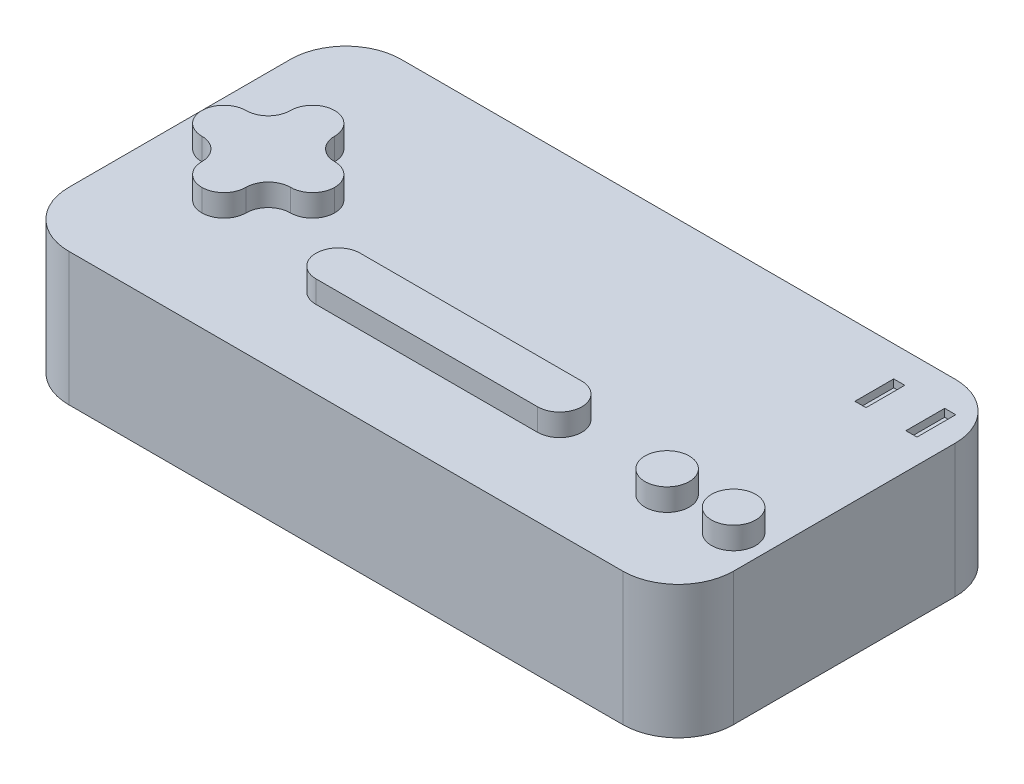
SolidWorks part; units mm, degrees
ref_plane "Front Plane" through (0, 0, 0) normal (0, 0, 1) x (1, 0, 0)
ref_plane "Top Plane" through (0, 0, 0) normal (0, 1, 0) x (1, 0, 0)
ref_plane "Right Plane" through (0, 0, 0) normal (1, 0, 0) x (0, 0, -1)
sketch "Sketch1" plane through (0, 0, 0) normal (0, 1, 0) x (1, 0, 0)
  line L1 (5, 0) -> (55, 0)
  line L2 (0, 5) -> (0, 25)
  line L3 (5, 30) -> (55, 30)
  line L4 (60, 5) -> (60, 25)
  arc A0 (0, 25) -> (5, 30) centre (5, 25) cw
  arc A1 (5, 0) -> (0, 5) centre (5, 5) cw
  arc A2 (55, 0) -> (60, 5) centre (55, 5) ccw
  arc A3 (55, 30) -> (60, 25) centre (55, 25) cw
  point P7 (0, 30)
  point P10 (0, 0)
  point P13 (60, 0)
  point P16 (60, 30)
  dimension "D3" = 5
  dimension "D1" = 30
  dimension "D2" = 60
extrude "Boss-Extrude1" add sketch "Sketch1" along normal blind 12
sketch "Sketch2" plane through (0, 12, 0) normal (0, 1, 0) x (1, 0, 0)
  line L0 (2, 17) -> (2, 13)
  line L1 (2, 13) -> (6, 13)
  line L2 (6, 13) -> (6, 9)
  line L3 (6, 9) -> (10, 9)
  line L4 (10, 9) -> (10, 13)
  line L5 (10, 13) -> (14, 13)
  line L6 (14, 13) -> (14, 17)
  line L7 (14, 17) -> (10, 17)
  line L8 (10, 17) -> (10, 21)
  line L9 (10, 21) -> (6, 21)
  line L10 (6, 21) -> (6, 17)
  line L11 (2, 17) -> (6, 17)
  line L12 (20.3033, 9) -> (40.3033, 9) construction
  line L13 (20.3033, 11) -> (40.3033, 11)
  line L14 (20.3033, 7) -> (40.3033, 7)
  line L17 (60, 5) -> (60, 25) construction
  line L18 (54, 30) -> (54, 0) construction
  line L19 (55, 30) -> (5, 30) construction
  line L20 (5, 0) -> (55, 0) construction
  arc A0 (20.3033, 11) -> (20.3033, 7) centre (20.3033, 9) ccw
  arc A1 (40.3033, 7) -> (40.3033, 11) centre (40.3033, 9) ccw
  circle A2 centre (57, 8) radius 2
  circle A3 centre (51, 8) radius 2
  point P15 (30.3033, 9)
  point P33 (2, 15)
  dimension "D6" = 2
  dimension "D8" = 4
  dimension "D1" = 4
  dimension "D2" = 15
  dimension "D3" = 10
  dimension "D4" = 20
  dimension "D5" = 29.6967
  dimension "D7" = 6
  dimension "D9" = 57
  dimension "D10" = 8
extrude "Boss-Extrude2" add sketch "Sketch2" along normal blind 2
sketch "Sketch3" plane through (0, 12, 0) normal (0, 1, 0) x (1, 0, 0)
  line L0 (55, 30) -> (55, 0) construction
  line L1 (52.2, 27.25) -> (53.2, 27.25)
  line L2 (52.2, 27.25) -> (52.2, 23.75)
  line L3 (52.2, 23.75) -> (53.2, 23.75)
  line L4 (53.2, 27.25) -> (53.2, 23.75)
  line L11 (57.8, 23.75) -> (56.8, 23.75)
  line L12 (56.8, 27.25) -> (56.8, 23.75)
  line L13 (57.8, 27.25) -> (56.8, 27.25)
  line L14 (57.8, 27.25) -> (57.8, 23.75)
  arc A0 (60, 25) -> (55, 30) centre (55, 25) ccw construction
  dimension "D1" = 3.5
  dimension "D2" = 1
  dimension "D3" = 1.8
  dimension "D4" = 2.75
extrude "Cut-Extrude1" cut sketch "Sketch3" against normal blind 0.7
fillet "Fillet2" radius 2 12 edges at (6, 13, -9) (6, 13, -13) (2, 13, -13) (2, 13, -17) (6, 13, -17) (6, 13, -21) (10, 13, -21) (10, 13, -17) (14, 13, -17) (14, 13, -13) (10, 13, -13) (10, 13, -9)
